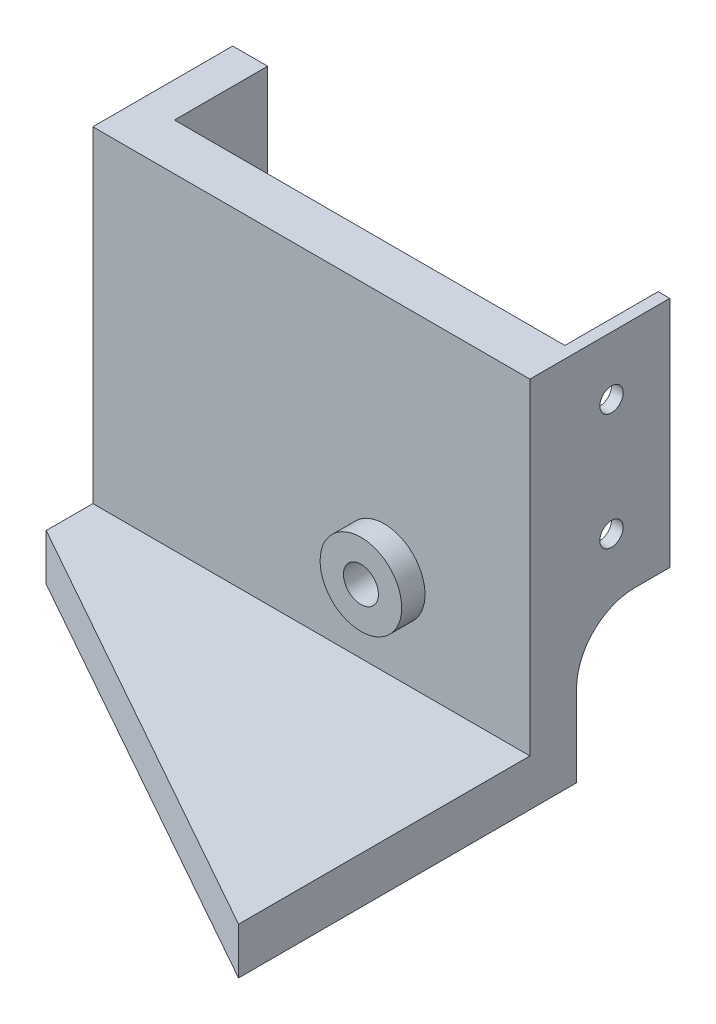
SolidWorks part; units mm, degrees
ref_plane "Front Plane" through (0, 0, 0) normal (0, 0, 1) x (1, 0, 0)
ref_plane "Top Plane" through (0, 0, 0) normal (0, 1, 0) x (1, 0, 0)
ref_plane "Right Plane" through (0, 0, 0) normal (1, 0, 0) x (0, 0, -1)
sketch "Sketch1" plane through (0, 0, 0) normal (0, 1, 0) x (1, 0, 0)
  line L1 (0, 0) -> (37.5, 0)
  line L2 (0, 0) -> (0, 12)
  line L3 (0, 12) -> (37.5, 12)
  line L4 (37.5, 0) -> (37.5, 12)
  line L5 (3, 12) -> (36.5, 12)
  line L6 (3, 12) -> (3, 4)
  line L7 (3, 4) -> (36.5, 4)
  line L8 (36.5, 12) -> (36.5, 4)
  dimension "D1" = 12
  dimension "D2" = 37.5
  dimension "D3" = 33.5
  dimension "D4" = 3
  dimension "D5" = 3
  dimension "10" = 8
extrude "Boss-Extrude1" add sketch "Sketch1" along normal blind 20 contours L3 L8 L7 L6 L2 L1 L4 region at (17.2775, 0, -3.0549)
sketch "Sketch2" plane through (0, 0, 0) normal (0, -1, 0) x (1, 0, 0)
  line L0 (37.5, 0) -> (37.5, -12) construction
  line L1 (0, 0) -> (37.5, 0)
  line L2 (0, 0) -> (0, -4)
  line L3 (0, -4) -> (37.5, -4)
  line L4 (37.5, 0) -> (37.5, -4)
extrude "Boss-Extrude2" add sketch "Sketch2" along normal blind 12
fillet "Fillet1" radius 5 2 edges at (1.5, 0, -4) (37, 0, -4)
sketch "Sketch3" plane through (0, 0, 0) normal (0, 0, 1) x (1, 0, 0)
  line L0 (37.5, 20) -> (37.5, -12) construction
  line L1 (0, -12) -> (37.5, -12)
  line L2 (0, -12) -> (0, -8)
  line L3 (0, -8) -> (37.5, -8)
  line L4 (37.5, -12) -> (37.5, -8)
  dimension "D1" = 4
extrude "Boss-Extrude3" add sketch "Sketch3" along normal blind 25 contours L3 L4 L1 L2
sketch "Sketch4" plane through (0, 0, 0) normal (0, 0, 1) x (1, 0, 0)
  line L0 (0, -8) -> (37.5, -8) construction
  line L1 (0, 20) -> (0, -8) construction
  circle A0 centre (25, -0.5) radius 1.5
  circle A1 centre (25, -0.5) radius 3.5
  dimension "D1" = 3
  dimension "D2" = 7.5
  dimension "D4" = 25
  dimension "D3" = 2
extrude "Boss-Extrude4" add sketch "Sketch4" along normal blind 2
sketch "Sketch5" plane through (0, 0, 2) normal (0, 0, 1) x (1, 0, 0)
  circle A0 centre (25, -0.5) radius 1.5 construction
  circle A1 centre (25, -0.5) radius 1.5
extrude "Cut-Extrude1" cut sketch "Sketch5" against normal through all contours A1
sketch "Sketch6" plane through (0, -8, 0) normal (0, 1, 0) x (1, 0, 0)
  line L0 (37.5, -25) -> (0, -4)
  line L3 (0, -25) -> (0, 0) construction
  line L4 (0, -4) -> (0, -25)
  line L5 (0, -25) -> (37.5, -25)
  dimension "D1" = 4
extrude "Cut-Extrude2" cut sketch "Sketch6" against normal blind 10
sketch "Sketch8" plane through (37.5, 0, 0) normal (1, 0, 0) x (0, 0, -1)
  circle A0 centre (7, 15) radius 1
  circle A1 centre (7, 5) radius 1
  dimension "D2" = 2
  dimension "D1" = 10
extrude "Cut-Extrude3" cut sketch "Sketch8" against normal through all both and the other way through all
